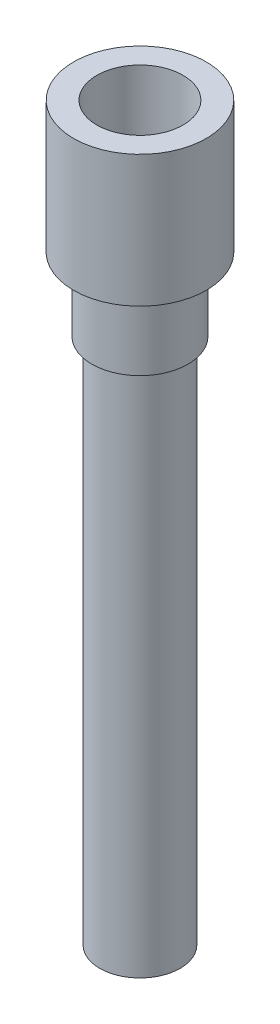
SolidWorks part; units mm, degrees
material "1023 Carbon Steel Sheet (SS)"
ref_plane "Front Plane" through (0, 0, 0) normal (0, 0, 1) x (1, 0, 0)
ref_plane "Top Plane" through (0, 0, 0) normal (0, 1, 0) x (1, 0, 0)
ref_plane "Right Plane" through (0, 0, 0) normal (1, 0, 0) x (0, 0, -1)
sketch "Sketch1" plane through (0, 0, 0) normal (0, 1, 0) x (1, 0, 0)
  circle A0 centre (0, 0) radius 2.58
  circle A1 centre (0, 0) radius 5.5
  circle A2 centre (0, 0) radius 4.58 construction
  dimension "D1" = 2
  dimension "D2" = 11
  dimension "D3" = 5.16
  dimension "D4" = 9.16
extrude "Boss-Extrude1" add sketch "Sketch1" along normal blind 72.14
sketch "Sketch2" plane through (0, 0, 0) normal (0, -1, 0) x (1, 0, 0)
  circle A0 centre (0, 0) radius 5.5
  circle A1 centre (0, 0) radius 5.5 construction
  circle A2 centre (0, 0) radius 5.5
  dimension "D1" = 11
sketch "Sketch4" plane through (0, 72.14, 0) normal (0, 1, 0) x (1, 0, 0)
  circle A0 centre (0, 0) radius 3.4
  circle A2 centre (0, 0) radius 5.5 construction
  dimension "D1" = 6.8
  dimension "D2" = 2.1
sketch "Sketch5" plane through (0, 72.14, 0) normal (0, 1, 0) x (1, 0, 0)
  circle A0 centre (0, 0) radius 6.5785
  circle M3 centre (0, 0) radius 5.5
  circle M4 centre (0, 0) radius 2.58
  dimension "D1" = 13.157
extrude "Boss-Extrude2" add sketch "Sketch5" along normal blind 10 contours M3 | A0 M3 | M4 region at (-6.3924, 72.14, 0) region at (-5.3444, 72.14, 0) region at (0, 72.14, 0)
sketch "Sketch6" plane through (0, 82.14, 0) normal (0, 1, 0) x (1, 0, 0)
  circle A0 centre (0, 0) radius 9.0785
  circle M9 centre (0, 0) radius 6.5785
  dimension "D1" = 18.157
extrude "Boss-Extrude3" add sketch "Sketch6" along normal blind 18 contours A0 | M9 region at (-8.8217, 82.14, 0) region at (0, 82.14, 0)
hole_wizard "G1/4 Tapped Hole2" positions "Sketch10" profile "Sketch11" tap size "G1/4" standard "ISO"
sketch "Sketch10" plane through (0, 100.14, 0) normal (0, 1, 0) x (1, 0, 0)
  point P0 (0, 0)
sketch "Sketch11" plane through (0, 100.14, 0) normal (1, 0, 0) x (0, 0, 1)
  line L0 (0, 0) -> (0, 18.5451)
  line L1 (0, 18.5451) -> (5.9, 15)
  line L2 (5.9, 15) -> (5.9, 0)
  line L5 (5.9, 0) -> (0, 0)
  line L10 (0, 18.5451) -> (-5.9, 15) construction
  line L11 (0, -6.35) -> (0, 107.95) construction
  dimension "Tap Drill Dia." = 11.8
  dimension "Tap Drill Depth" = 15
  dimension "Drill Angle" = 118
cosmetic thread "Hole Thread1" parameters "D1"=15, "D2"=13.157
ref_plane "Plane1" through (0, 88.14, 0) normal (0, -1, 0) x (-1, 0, 0)
sketch "Sketch15" plane through (0, 88.14, 0) normal (0, -1, 0) x (-1, 0, 0)
  circle A0 centre (0, 0) radius 2.5
  dimension "D1" = 5
extrude "Boss-Extrude4" add sketch "Sketch15" along normal up to surface (16 mm away) contours A0 region at (0, 88.14, 0) up to face at (0, 72.14, 2.58)
hole_wizard "M8 Tapped Hole1" positions "Sketch16" profile "Sketch17" tap size "M8" standard "ISO"
sketch "Sketch16" plane through (0, 88.14, 0) normal (0, 1, 0) x (1, 0, 0)
  point P0 (0, 0)
sketch "Sketch17" plane through (0, 88.14, 0) normal (1, 0, 0) x (0, 0, 1)
  line L0 (0, 0) -> (0, 81.1829)
  line L1 (0, 81.1829) -> (3.4, 79.14)
  line L2 (3.4, 79.14) -> (3.4, 0)
  line L5 (3.4, 0) -> (0, 0)
  line L10 (0, 81.1829) -> (-3.4, 79.14) construction
  line L11 (0, -6.35) -> (0, 107.95) construction
  dimension "Tap Drill Dia." = 6.8
  dimension "Tap Drill Depth" = 79.14
  dimension "Drill Angle" = 118
cosmetic thread "Hole Thread2" parameters "D1"=10, "D2"=8
equation "\"D1@Sketch6\"=13.157+2.5*2"
